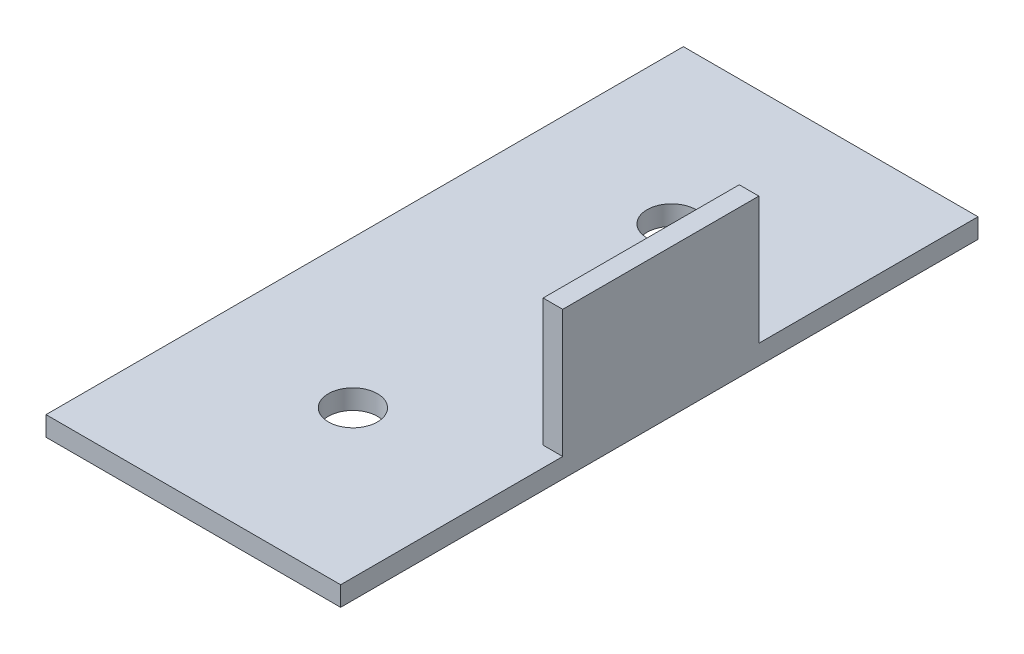
SolidWorks part; units mm, degrees
ref_plane "Спереди" through (0, 0, 0) normal (0, 0, 1) x (1, 0, 0)
ref_plane "Сверху" through (0, 0, 0) normal (0, 1, 0) x (1, 0, 0)
ref_plane "Справа" through (0, 0, 0) normal (1, 0, 0) x (0, 0, -1)
sketch "Эскиз1" plane through (0, 0, 0) normal (0, 0, 1) x (1, 0, 0)
  line L0 (0, 0) -> (-28.0486, 0)
  line L1 (0, 0) -> (0, 30)
extrude "Вытянуть-Тонкостенный1" add sketch "Эскиз1" along normal blind 20 thin thin type one direction wall 2
sketch "Эскиз4" plane through (2, 0, 0) normal (1, 0, 0) x (0, 0, -1)
  line L0 (-20, 30) -> (0, 30)
  line L1 (0, 30) -> (0, 13)
  line L2 (0, 13) -> (-20, 13)
  line L3 (-20, 13) -> (-20, 30)
extrude "Вырез-Вытянуть1" cut sketch "Эскиз4" against normal through all
sketch "Эскиз6" plane through (0, 0, 0) normal (0, 1, 0) x (1, 0, 0)
  line L0 (2, -42.65) -> (2, 22.35) construction
  line L1 (-28.0486, 0) -> (2, 0)
  line L2 (-28.0486, 0) -> (-28.0486, 22.35)
  line L3 (-28.0486, 22.35) -> (2, 22.35)
  line L4 (2, 0) -> (2, 22.35)
  line L5 (-28.0486, -20) -> (2, -20)
  line L6 (-28.0486, -20) -> (-28.0486, -42.65)
  line L7 (-28.0486, -42.65) -> (2, -42.65)
  line L8 (2, -20) -> (2, -42.65)
extrude "Вытянуть1" add sketch "Эскиз6" against normal blind 2
sketch "Эскиз7" plane through (0, 0, 0) normal (0, 1, 0) x (1, 0, 0)
  circle A0 centre (-13, 6.1) radius 2.5
  circle A1 centre (-13, -26.4) radius 2.5
extrude "Вырез-Вытянуть2" cut sketch "Эскиз7" against normal through all
